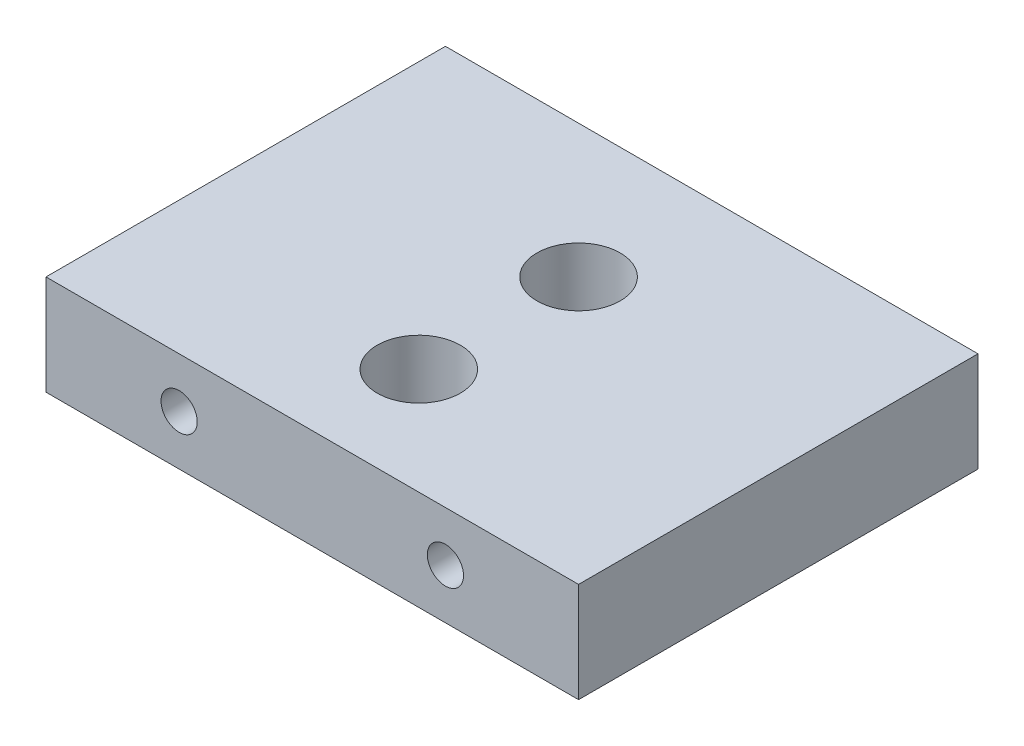
SolidWorks part; units mm, degrees
ref_plane "Front Plane" through (0, 0, 0) normal (0, 0, 1) x (1, 0, 0)
ref_plane "Top Plane" through (0, 0, 0) normal (0, 1, 0) x (1, 0, 0)
ref_plane "Right Plane" through (0, 0, 0) normal (1, 0, 0) x (0, 0, -1)
sketch "Sketch1" plane through (0, 0, 0) normal (0, 0, 1) x (1, 0, 0)
  line L0 (-25.4, -50.8) -> (-25.4, 50.8) construction
  line L1 (25.4, -4.7625) -> (-25.4, -4.7625)
  line L2 (25.4, -4.7625) -> (25.4, 4.7625)
  line L3 (25.4, 4.7625) -> (-25.4, 4.7625)
  line L4 (-25.4, -4.7625) -> (-25.4, 4.7625)
  line L5 (25.4, -4.7625) -> (-25.4, 4.7625) construction
  line L6 (25.4, 4.7625) -> (-25.4, -4.7625) construction
  circle A1 centre (-12.7, 0) radius 2.2479 construction
  circle A2 centre (12.7, 0) radius 2.2479 construction
  circle A5 centre (-12.7, 0) radius 2.2479
  circle A6 centre (12.7, 0) radius 2.2479
  point P0 (0, 0)
  dimension "D1" = 9.525
extrude "Boss-Extrude1" add sketch "Sketch1" along normal blind 38.1 contours L1 L4 L3 L2
hole_wizard "5/16 (0.3125) Diameter Hole1" positions "Sketch4" profile "Sketch5" hole size "5/16" standard "ANSI Inch" end condition through all
sketch "Sketch4" plane through (0, -4.7625, 0) normal (0, -1, 0) x (-1, 0, 0)
  line L0 (-25.4, -38.1) -> (25.4, -38.1) construction
  point P0 (0, -12.7)
  point P2 (0, -27.94)
  point P7 (0, -38.1)
  dimension "D1" = 15.24
  dimension "D2" = 10.16
sketch "Sketch5" plane through (0, -4.7625, 12.7) normal (1, 0, 0) x (0, 0, -1)
  line L0 (0, 0) -> (0, 9.525)
  line L1 (0, 9.525) -> (3.9687, 9.525)
  line L2 (3.9687, 9.525) -> (3.9688, 0)
  line L5 (3.9688, 0) -> (0, 0)
  line L11 (0, -6.35) -> (0, 107.95) construction
  dimension "Thru Hole Dia." = 7.9375
  dimension "Thru Hole Depth" = 9.525
hole_wizard "#8-36 Tapped Hole1" positions "Sketch8" profile "Sketch7" tap size "#8-36" standard "ANSI Inch" end condition through all
sketch "Sketch8" plane through (0, 0, 0) normal (0, 0, -1) x (-1, 0, 0)
  point P2 (-12.7, 0)
  point P4 (12.7, 0)
  point P18 (0, 0)
  point P19 (0, 0)
sketch "Sketch7" plane through (12.7, 0, 0) normal (1, 0, 0) x (0, 1, 0)
  line L0 (0, 0) -> (0, 38.1)
  line L1 (0, 38.1) -> (1.7272, 38.1)
  line L2 (1.7272, 38.1) -> (1.7272, 0)
  line L5 (1.7272, 0) -> (0, 0)
  line L11 (0, -6.35) -> (0, 107.95) construction
  dimension "Thru Tap Drill Dia." = 3.4544
  dimension "Thru Tap Drill Depth" = 38.1
cosmetic thread "Hole Thread2" parameters "D2"=4.1656
cosmetic thread "Hole Thread3" parameters "D2"=4.1656
equation "\"TabDepth\"= 1.5"
equation "\"D1@Boss-Extrude1\"=\"TabDepth\""
